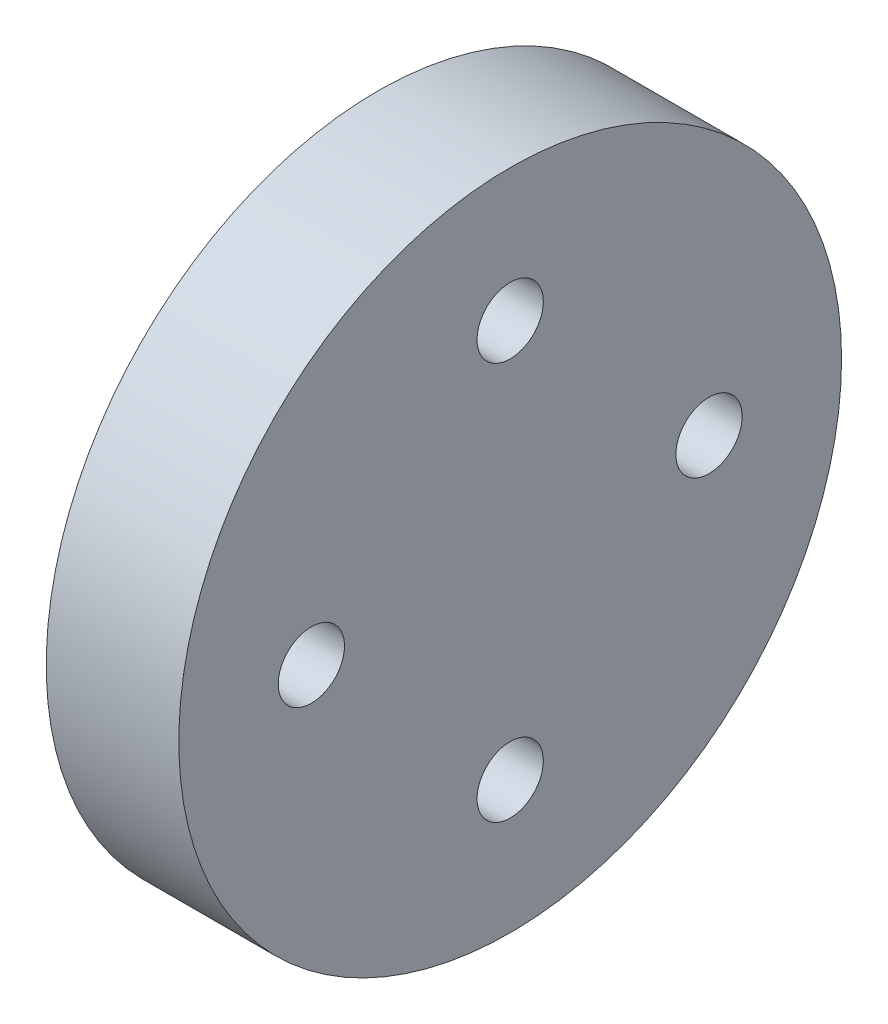
SolidWorks part; units mm, degrees
ref_plane "前视基准面" through (0, 0, 0) normal (0, 0, 1) x (1, 0, 0)
ref_plane "上视基准面" through (0, 0, 0) normal (0, 1, 0) x (1, 0, 0)
ref_plane "右视基准面" through (0, 0, 0) normal (1, 0, 0) x (0, 0, -1)
other "Configuration Table"
sketch "Sketch1" plane through (0, 0, 0) normal (1, 0, 0) x (0, 0, -1)
  circle A0 centre (0, 0) radius 25
extrude "Boss-Extrude1" add sketch "Sketch1" along normal blind 10
sketch "Sketch2" plane through (0, 0, 0) normal (1, 0, 0) x (0, 0, -1)
  circle A0 centre (-15, 0) radius 2.5
  circle A1 centre (15, 0) radius 2.5
  circle A2 centre (0, 15) radius 2.5
  circle A3 centre (0, -15) radius 2.5
extrude "Cut-Extrude1" cut sketch "Sketch2" along normal blind 10
sketch3d "3DSketch1"
  line L0 (0, 0, 0) -> (0, 0, 100) construction
ref_axis "Axis_Main" through (0, 0, 0) along (0, 0, 1)
ref_plane "Mate_Face" through (0, 0, 0) normal (1, 0, 0) x (0, 0, -1)
